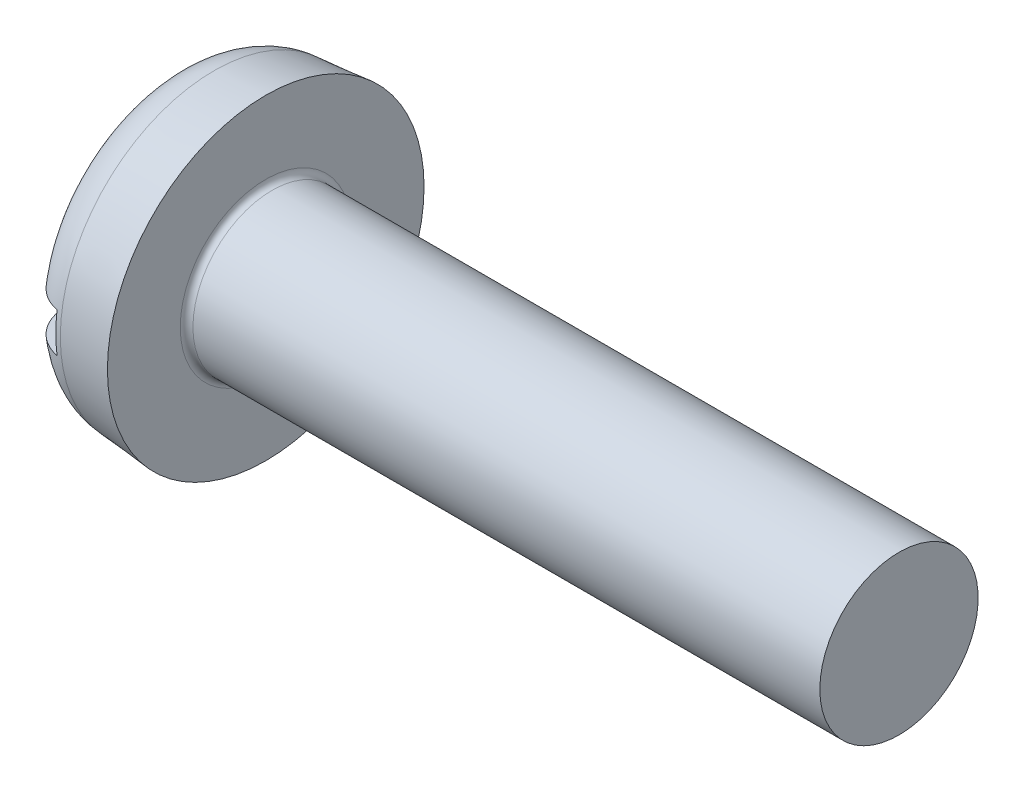
SolidWorks part; units mm, degrees
ref_plane "Front Plane" through (0, 0, 0) normal (0, 0, 1) x (1, 0, 0)
ref_plane "Top Plane" through (0, 0, 0) normal (0, 1, 0) x (1, 0, 0)
ref_plane "Right Plane" through (0, 0, 0) normal (1, 0, 0) x (0, 0, -1)
sketch "BodySke" plane through (0, 0, 0) normal (0, 0, 1) x (1, 0, 0)
  line L0 (0, 0) -> (111.3824, 0) construction
  line L1 (0, 0) -> (0, 9.4751)
  line L2 (0, 9.4751) -> (6, 10)
  line L3 (6, 10) -> (6, 5)
  line L4 (6, 5) -> (46, 5)
  line L5 (46, 5) -> (46, 0)
  line L6 (7.5, 8.824) -> (7.5, -5.8939) construction
  line L7 (0, 0) -> (46, 0)
  line L8 (8, 8.824) -> (8, -4.958) construction
  point P10 (46, 4.172)
  dimension "Thread_minor" = 8.344
  dimension "Advance" = 1.5
revolve "BaseBody" add sketch "BodySke" angle 360 about L0
cosmetic thread "ThreadCosmetic" [suppressed] parameters "Thread_minor"=8.344
fillet "Fillet_head" radius 3 1 edges at (0, 0, 9.4751)
fillet "Fillet2" radius 0.4 1 edges at (6, 0, 5)
sketch "SlotSke" plane through (0, 0, 0) normal (-1, 0, 0) x (0, 0, 1)
  line L1 (-10, 1.25) -> (10, 1.25)
  line L2 (-10, 1.25) -> (-10, -1.25)
  line L3 (-10, -1.25) -> (10, -1.25)
  line L4 (10, 1.25) -> (10, -1.25)
  dimension "D1" = 20
  dimension "D2" = 10
  dimension "D3" = 1.25
extrude "Slot" cut sketch "SlotSke" against normal blind 2.4
sketch "ThdSchSke" plane through (0, 0, 0) normal (0, 0, 1) x (1, 0, 0)
  line L0 (0, 0) -> (55.1256, 0) construction
  line L1 (0, 0) -> (111.3824, 0) construction
  line L2 (45.522, 5) -> (45.522, 5.9561)
  line L3 (45.522, 5.9561) -> (46.478, 5.9561)
  line L4 (46.478, 5.9561) -> (46.478, 5)
  line L5 (46.478, 5) -> (46, 4.172)
  line L6 (46, 4.172) -> (45.522, 5)
  line L7 (6, 5) -> (46, 5) construction
  line L13 (46, 5) -> (46, 0) construction
revolve "ThreadSchematic" [suppressed] cut sketch "ThdSchSke" angle 360 about L0
pattern_linear "ThdSchPat" [suppressed] count 25 along (-1, 0, 0) of bodies 103
equation "\"Thread_minor@ThreadCosmetic\" = \"Thread_minor@BodySke\""
equation "\"D1@SlotSke\" = \"Head_dia@BodySke\""
equation "\"D2@SlotSke\" = \"D1@SlotSke\" / 2"
equation "\"D3@SlotSke\" = \"Slot_width@SlotSke\" / 2"
equation "\"Advance@ThdSchPat\" = \"Advance@BodySke\""
equation "\"D1@ThdSchPat\" =  int( \"Thread_length@BodySke\" /\"Advance@ThdSchPat\" ) "
